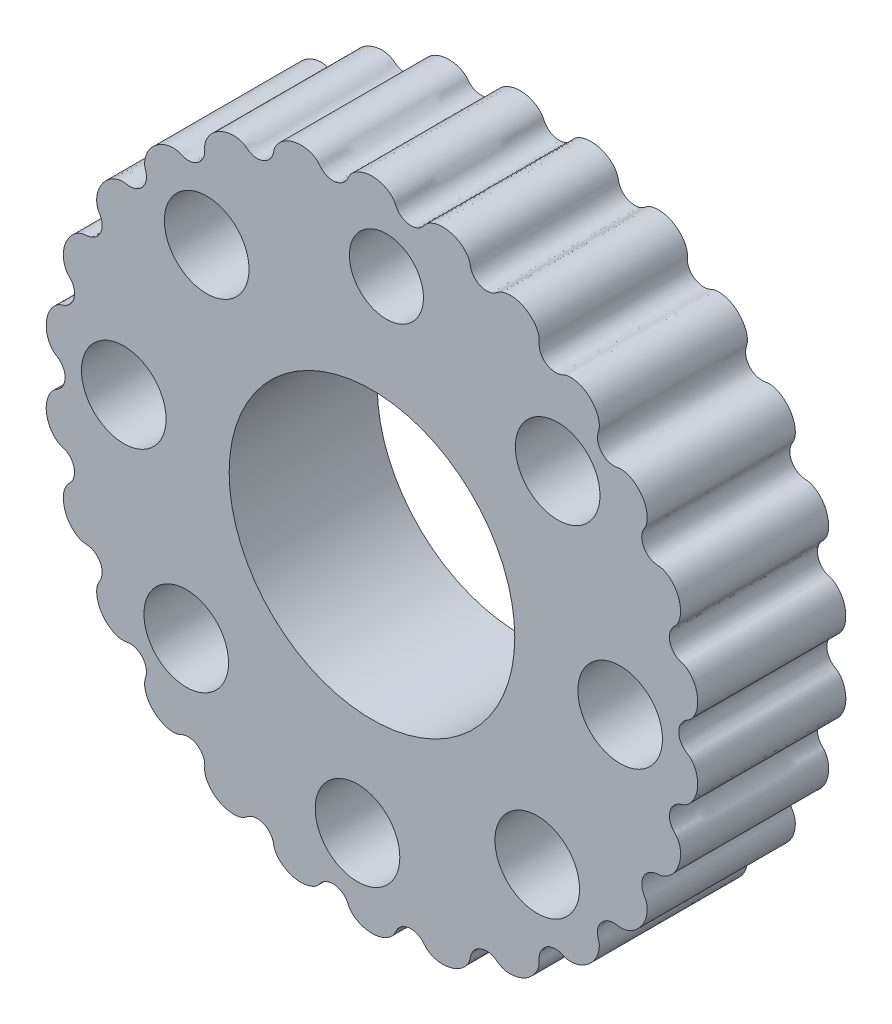
SolidWorks part; units mm, degrees
ref_plane "Front Plane" through (0, 0, 0) normal (0, 0, 1) x (1, 0, 0)
ref_plane "Top Plane" through (0, 0, 0) normal (0, 1, 0) x (1, 0, 0)
ref_plane "Right Plane" through (0, 0, 0) normal (1, 0, 0) x (0, 0, -1)
ref_plane "Plane1"
sketch "Sketch1" plane through (0, 0, 0) normal (0, 0, 1) x (1, 0, 0)
  circle A0 centre (23.4602, -1.3664) radius 4
  circle A1 centre (17.5551, 15.6227) radius 4
  circle A2 centre (1.3664, 23.4602) radius 4
  circle A3 centre (-15.6227, 17.5551) radius 4
  circle A4 centre (-23.4602, 1.3664) radius 4
  circle A5 centre (-17.5551, -15.6227) radius 4
  circle A6 centre (-1.3664, -23.4602) radius 4
  circle A7 centre (15.6227, -17.5551) radius 4
  circle A8 centre (0, 0) radius 13.5
  spline S0 degree 3 poles (29, 0) (29, -0.3768) (29.1535, -0.7032) (29.2804, -0.8839) (29.4951, -1.1897) (29.6235, -1.2426) (29.7, -1.2958) (29.8542, -1.4032) (29.8827, -1.413) (29.9346, -1.4485) (30.0574, -1.5322) (30.2266, -1.6673) (30.4081, -1.9555) (30.6633, -2.3609) (30.8614, -3.0668) (30.7707, -3.763) (30.6897, -4.3835) (30.3903, -4.9545) (30.0794, -5.2897) (29.8505, -5.5365) (29.6366, -5.6604) (29.4954, -5.7232) (29.4221, -5.7558) (29.3787, -5.7696) (29.2726, -5.805) (29.2187, -5.823) (29.1538, -5.8344) (28.9703, -5.9277) (28.8487, -5.9895) (28.6383, -6.0836) (28.4024, -6.4106) (28.2302, -6.6494) (28.1014, -7.0439) (28.114, -7.3663) (28.13, -7.7749) (28.2721, -8.0058) (28.3561, -8.139) (28.5057, -8.3761) (28.5682, -8.4123) (28.6126, -8.4587) (28.7112, -8.5615) (28.7444, -8.5938) (28.8088, -8.6819) (28.9486, -8.8731) (29.1514, -9.2784) (29.1753, -9.8433) (29.2016, -10.4629) (28.9684, -11.2228) (28.5673, -11.7445) (28.2242, -12.1907) (27.7962, -12.4491) (27.512, -12.5503) (27.3588, -12.6048) (27.2544, -12.621) (27.1583, -12.631) (27.0994, -12.6372) (27.0677, -12.6315) (26.8731, -12.6585) (26.7882, -12.6702) (26.6656, -12.6757) (26.4169, -12.7864) (26.2329, -12.8684) (25.9467, -13.0438) (25.7404, -13.3693) (25.5449, -13.678) (25.4898, -14.0569) (25.5065, -14.2975) (25.5338, -14.6901) (25.6313, -14.8203) (25.6773, -14.913) (25.7672, -15.0947) (25.7908, -15.1176) (25.819, -15.1687) (25.8858, -15.2896) (25.9587, -15.4408) (26.0003, -15.7215) (26.0635, -16.1484) (25.9783, -16.8383) (25.624, -17.4359) (25.2735, -18.0271) (24.6847, -18.475) (24.2049, -18.6519) (23.8505, -18.7825) (23.5839, -18.7865) (23.4237, -18.7723) (23.3532, -18.766) (23.3135, -18.758) (23.193, -18.7391) (23.1305, -18.7293) (23.0571, -18.7044) (22.817, -18.7127) (22.666, -18.718) (22.4117, -18.7282) (22.0741, -18.9277) (21.8037, -19.0874) (21.537, -19.4066) (21.4267, -19.6888) (21.2703, -20.0892) (21.3164, -20.3323) (21.3352, -20.4729) (21.3697, -20.7318) (21.4008, -20.775) (21.4173, -20.8314) (21.4554, -20.962) (21.476, -21.0337) (21.4871, -21.194) (21.5077, -21.4931) (21.432, -22.0351) (21.1005, -22.5638) (20.7525, -23.1188) (20.1283, -23.5982) (19.5445, -23.7905) (19.0833, -23.9425) (18.6768, -23.9306) (18.4374, -23.8827) (18.3183, -23.8589) (18.2417, -23.8315) (18.1648, -23.8002) (18.1153, -23.78) (18.0821, -23.7599) (17.9302, -23.7036) (17.8502, -23.674) (17.7421, -23.6178) (17.4519, -23.5986) (17.2532, -23.5854) (16.9238, -23.6055) (16.5911, -23.7932) (16.2828, -23.9672) (16.0549, -24.2657) (15.9532, -24.4853) (15.7864, -24.8455) (15.8095, -25.0146) (15.8061, -25.1217) (15.7995, -25.3288) (15.8106, -25.3619) (15.8121, -25.419) (15.8156, -25.554) (15.8124, -25.7044) (15.7327, -25.9537) (15.6076, -26.3448) (15.2434, -26.9124) (14.671, -27.2924) (14.1247, -27.6552) (13.4277, -27.8145) (12.9077, -27.7783) (12.4959, -27.7496) (12.2125, -27.6253) (12.0576, -27.5329) (11.9881, -27.4915) (11.9482, -27.4616) (11.8709, -27.4033) (11.8233, -27.3673) (11.7888, -27.3192) (11.5576, -27.1982) (11.4393, -27.1363) (11.2501, -27.0314) (10.8867, -27.0172) (10.599, -27.006) (10.2014, -27.1117) (9.9356, -27.3019) (9.6266, -27.5231) (9.5017, -27.7618) (9.4329, -27.9087) (9.301, -28.1902) (9.3096, -28.2703) (9.2956, -28.3375) (9.2644, -28.4872) (9.2586, -28.5276) (9.225, -28.6271) (9.1526, -28.842) (8.9513, -29.2246) (8.5213, -29.5648) (8.0513, -29.9367) (7.3217, -30.1953) (6.6665, -30.1855) (6.1495, -30.1778) (5.702, -30.0198) (5.428, -29.8555) (5.2317, -29.7378) (5.1254, -29.6318) (5.0489, -29.545) (5.0104, -29.5012) (4.9895, -29.4704) (4.8985, -29.3641) (4.8484, -29.3055) (4.797, -29.2149) (4.5489, -29.0464) (4.3992, -28.9447) (4.1364, -28.7982) (3.7557, -28.7793) (3.4144, -28.7624) (3.0427, -28.892) (2.8246, -29.0387) (2.4844, -29.2675) (2.4056, -29.4474) (2.3446, -29.5491) (2.2297, -29.7406) (2.2241, -29.781) (2.1999, -29.8314) (2.143, -29.9499) (2.0908, -30.0507) (1.9482, -30.2096) (1.7042, -30.4816) (1.1811, -30.8377) (0.5184, -30.9547) (-0.1433, -31.0716) (-0.8912, -30.9256) (-1.3839, -30.6514) (-1.7244, -30.4618) (-1.9423, -30.2342) (-2.0587, -30.0727) (-2.1328, -29.9699) (-2.1641, -29.907) (-2.2104, -29.8094) (-2.2297, -29.7686) (-2.2472, -29.7236) (-2.3086, -29.6118) (-2.354, -29.5292) (-2.4036, -29.3984) (-2.6485, -29.1765) (-2.8114, -29.029) (-3.1148, -28.8364) (-3.4891, -28.7894) (-3.8512, -28.7438) (-4.1885, -28.8477) (-4.3847, -28.9488) (-4.7171, -29.1199) (-4.7917, -29.2448) (-4.8562, -29.3161) (-4.9839, -29.457) (-4.9977, -29.4858) (-5.0369, -29.5312) (-5.1335, -29.6432) (-5.276, -29.7878) (-5.5725, -29.9342) (-5.9813, -30.1361) (-6.6691, -30.2631) (-7.3372, -30.1181) (-8.0054, -29.9731) (-8.5993, -29.5653) (-8.9067, -29.1864) (-9.1084, -28.9378) (-9.1972, -28.7228) (-9.2396, -28.5812) (-9.2583, -28.5188) (-9.2682, -28.4729) (-9.2832, -28.3986) (-9.2922, -28.3537) (-9.2988, -28.3029) (-9.3344, -28.1756) (-9.3615, -28.0789) (-9.3833, -27.9276) (-9.5864, -27.6486) (-9.7241, -27.4594) (-10.0027, -27.2036) (-10.3581, -27.0894) (-10.7123, -26.9756) (-11.0474, -27.018) (-11.2473, -27.0744) (-11.6072, -27.1758) (-11.6905, -27.2733) (-11.7631, -27.3241) (-11.9144, -27.4301) (-11.9326, -27.4513) (-11.9905, -27.4903) (-12.1265, -27.582) (-12.364, -27.7112) (-12.7623, -27.7637) (-13.2625, -27.8296) (-13.98, -27.7125) (-14.5617, -27.3617) (-15.1424, -27.0114) (-15.5442, -26.46) (-15.6987, -26.0512) (-15.796, -25.7936) (-15.8116, -25.6098) (-15.8127, -25.4806) (-15.8131, -25.431) (-15.8112, -25.3906) (-15.8081, -25.3148) (-15.806, -25.2642) (-15.7987, -25.2039) (-15.8099, -25.0483) (-15.8182, -24.933) (-15.8173, -24.7503) (-15.978, -24.4341) (-16.0929, -24.2081) (-16.344, -23.9163) (-16.6528, -23.7603) (-17.0099, -23.5797) (-17.3332, -23.5839) (-17.5212, -23.6047) (-17.8534, -23.6414) (-17.9327, -23.7033) (-18.0037, -23.7323) (-18.1561, -23.7944) (-18.1838, -23.8103) (-18.262, -23.8364) (-18.4404, -23.8958) (-18.7757, -23.9629) (-19.2368, -23.8716) (-19.7732, -23.7654) (-20.4268, -23.4061) (-20.8581, -22.8954) (-21.2862, -22.3886) (-21.4709, -21.7796) (-21.4889, -21.3946) (-21.5006, -21.1457) (-21.4689, -21.0138) (-21.4316, -20.881) (-21.4196, -20.8384) (-21.4053, -20.798) (-21.3781, -20.6911) (-21.3584, -20.6139) (-21.3146, -20.5126) (-21.3209, -20.2211) (-21.3252, -20.0275) (-21.3677, -19.6993) (-21.5965, -19.3708) (-21.805, -19.0713) (-22.1447, -18.8656) (-22.3836, -18.7883) (-22.7753, -18.6615) (-22.9389, -18.7099) (-23.0449, -18.72) (-23.2441, -18.739) (-23.2757, -18.7532) (-23.3323, -18.7614) (-23.4706, -18.7816) (-23.6339, -18.7969) (-23.9104, -18.7378) (-24.318, -18.6506) (-24.9112, -18.3483) (-25.344, -17.8314) (-25.7763, -17.3151) (-26.009, -16.6207) (-26.0223, -16.0997) (-26.0305, -15.7796) (-25.9715, -15.5311) (-25.9128, -15.3722) (-25.8794, -15.2821) (-25.8488, -15.2219) (-25.8135, -15.1588) (-25.7908, -15.1181) (-25.7677, -15.0833) (-25.7129, -14.9818) (-25.6787, -14.9186) (-25.6238, -14.8384) (-25.5603, -14.6098) (-25.5153, -14.4476) (-25.4561, -14.1735) (-25.552, -13.8037) (-25.6387, -13.4698) (-25.8918, -13.1306) (-26.1184, -12.9613) (-26.4466, -12.7161) (-26.6525, -12.6984) (-26.7739, -12.6749) (-26.9988, -12.6314) (-27.0428, -12.6411) (-27.0985, -12.6365) (-27.2342, -12.6254) (-27.3357, -12.6149) (-27.5268, -12.5449) (-27.8511, -12.4261) (-28.3537, -12.0954) (-28.7066, -11.5466) (-29.0604, -10.9965) (-29.2219, -10.2615) (-29.1644, -9.6901) (-29.1166, -9.2153) (-28.9463, -8.8757) (-28.8213, -8.6992) (-28.7612, -8.6144) (-28.7198, -8.5699) (-28.6508, -8.4983) (-28.6171, -8.4633) (-28.5778, -8.4304) (-28.4799, -8.3105) (-28.416, -8.2322) (-28.3073, -8.1242) (-28.1992, -7.8144) (-28.123, -7.5961) (-28.071, -7.229) (-28.1747, -6.8756) (-28.2827, -6.5076) (-28.5171, -6.2492) (-28.6801, -6.1162) (-28.9604, -5.8874) (-29.0858, -5.8722) (-29.1681, -5.8416) (-29.337, -5.7787) (-29.3662, -5.775) (-29.4289, -5.7508) (-29.5759, -5.6941) (-29.8003, -5.5836) (-30.0604, -5.31) (-30.3935, -4.9595) (-30.7169, -4.3332) (-30.7818, -3.6653) (-30.8458, -3.0063) (-30.656, -2.3551) (-30.4157, -1.9677) (-30.2771, -1.7444) (-30.1351, -1.6043) (-30.0301, -1.5193) (-29.9574, -1.4605) (-29.9166, -1.4356) (-29.8137, -1.3706) (-29.7667, -1.341) (-29.708, -1.3143) (-29.5579, -1.1868) (-29.4553, -1.0998) (-29.2724, -0.9632) (-29.1161, -0.5848) (-29.0009, -0.3057) (-28.9698, 0.1259) (-29.0654, 0.4425) (-29.1841, 0.8355) (-29.3773, 1.0194) (-29.4897, 1.1258) (-29.6904, 1.3157) (-29.7572, 1.3349) (-29.8106, 1.3687) (-29.9298, 1.444) (-29.9717, 1.4689) (-30.0584, 1.5428) (-30.2439, 1.701) (-30.5415, 2.06) (-30.6943, 2.6142) (-30.8613, 3.2202) (-30.8013, 4.0179) (-30.5269, 4.6132) (-30.2894, 5.1284) (-29.9282, 5.4693) (-29.6815, 5.6237) (-29.5751, 5.6903) (-29.4924, 5.7268) (-29.4191, 5.7546) (-29.3615, 5.7764) (-29.3277, 5.7831) (-29.1802, 5.8371) (-29.1098, 5.8629) (-29.0101, 5.8851) (-28.7932, 6.032) (-28.6486, 6.13) (-28.4211, 6.3101) (-28.2591, 6.6536) (-28.115, 6.959) (-28.0901, 7.3587) (-28.146, 7.6238) (-28.233, 8.0358) (-28.3787, 8.1814) (-28.4539, 8.278) (-28.5962, 8.4604) (-28.6326, 8.479) (-28.6715, 8.5199) (-28.763, 8.6159) (-28.8382, 8.6995) (-28.9365, 8.8892) (-29.1068, 9.218) (-29.2558, 9.8476) (-29.1217, 10.5193) (-28.9876, 11.1907) (-28.5674, 11.8414) (-28.1295, 12.1955) (-27.7806, 12.4777) (-27.461, 12.5803) (-27.2753, 12.6144) (-27.1996, 12.6284) (-27.1508, 12.6324) (-27.058, 12.6397) (-27.0015, 12.6441) (-26.9433, 12.6361) (-26.7233, 12.6854) (-26.6027, 12.7125) (-26.4096, 12.7473) (-26.1284, 12.9539) (-25.9109, 13.1136) (-25.6628, 13.4275) (-25.5663, 13.7523) (-25.453, 14.134) (-25.5114, 14.4283) (-25.5572, 14.5982) (-25.6376, 14.8968) (-25.7013, 14.962) (-25.7367, 15.0249) (-25.8126, 15.1598) (-25.8327, 15.1886) (-25.8686, 15.2659) (-25.9518, 15.4452) (-26.061, 15.7967) (-26.01, 16.2903) (-25.9515, 16.8559) (-25.6388, 17.5553) (-25.1623, 18.0295) (-24.7487, 18.441) (-24.2464, 18.6693) (-23.892, 18.7416) (-23.6537, 18.7902) (-23.494, 18.7817) (-23.375, 18.7672) (-23.3156, 18.7599) (-23.2803, 18.7506) (-23.1376, 18.7309) (-23.061, 18.7203) (-22.9621, 18.6866) (-22.6645, 18.7252) (-22.4847, 18.7486) (-22.1905, 18.8139) (-21.8935, 19.0526) (-21.627, 19.2669) (-21.4355, 19.6104) (-21.37, 19.8646) (-21.2676, 20.2613) (-21.328, 20.4476) (-21.3498, 20.564) (-21.3908, 20.7831) (-21.4134, 20.817) (-21.4287, 20.8708) (-21.4646, 20.9971) (-21.4925, 21.1077) (-21.4909, 21.322) (-21.4883, 21.6876) (-21.3324, 22.3006) (-20.9141, 22.8271) (-20.4969, 23.3522) (-19.8418, 23.7383) (-19.2919, 23.8601) (-18.9242, 23.9415) (-18.6172, 23.9206) (-18.4224, 23.8796) (-18.3156, 23.8572) (-18.2436, 23.8318) (-18.1736, 23.8037) (-18.1304, 23.7864) (-18.0938, 23.7688) (-17.9991, 23.7304) (-17.9282, 23.7016) (-17.8468, 23.6417) (-17.5259, 23.6052) (-17.3453, 23.5847) (-17.0425, 23.5774) (-16.6954, 23.7395) (-16.3857, 23.8842) (-16.1186, 24.1719) (-15.9945, 24.4026) (-15.8013, 24.7619) (-15.8149, 24.9569) (-15.8082, 25.075) (-15.7955, 25.2966) (-15.8092, 25.3354) (-15.8112, 25.3912) (-15.8159, 25.5219) (-15.8166, 25.6338) (-15.7656, 25.8382) (-15.6784, 26.1874) (-15.3894, 26.7385) (-14.8669, 27.1506) (-14.3457, 27.5617) (-13.6251, 27.7892) (-13.0592, 27.7842) (-12.6994, 27.7811) (-12.4096, 27.6997) (-12.223, 27.6178) (-12.089, 27.5589) (-12.0124, 27.5078) (-11.9354, 27.4515) (-11.8996, 27.4253) (-11.8677, 27.3989) (-11.7841, 27.339) (-11.7249, 27.2966) (-11.6545, 27.2288) (-11.4118, 27.1307) (-11.2514, 27.0658) (-10.9753, 26.9745) (-10.591, 27.0342) (-10.2451, 27.088) (-9.8867, 27.3072) (-9.6991, 27.511) (-9.423, 27.811) (-9.3864, 28.0067) (-9.3505, 28.1214) (-9.2836, 28.3352) (-9.2876, 28.3777) (-9.2763, 28.4322) (-9.2486, 28.5659) (-9.2229, 28.6754) (-9.1199, 28.868) (-8.9499, 29.1858) (-8.5383, 29.6467) (-7.9371, 29.9196) (-7.3363, 30.1923) (-6.5877, 30.2423) (-6.0406, 30.1047) (-5.6141, 29.9974) (-5.3226, 29.8039) (-5.1687, 29.6659) (-5.092, 29.5972) (-5.0504, 29.5488) (-4.993, 29.4787) (-4.9629, 29.4418) (-4.9364, 29.402) (-4.8378, 29.296) (-4.7759, 29.2295) (-4.6957, 29.124) (-4.4418, 28.9797) (-4.2603, 28.8765) (-3.9418, 28.7541) (-3.5679, 28.7815) (-3.1975, 28.8087) (-2.8689, 28.9896) (-2.691, 29.1394) (-2.3931, 29.3903) (-2.3498, 29.5357) (-2.3028, 29.6225) (-2.2089, 29.7958) (-2.2036, 29.8258) (-2.1759, 29.8802) (-2.1105, 30.0087) (-2.0098, 30.1776) (-1.7682, 30.3852) (-1.4156, 30.6881) (-0.7524, 30.9888) (-0.0462, 30.9996) (0.5923, 31.0095) (1.2195, 30.7852) (1.605, 30.5124) (1.8911, 30.3099) (2.0459, 30.1047) (2.1271, 29.9687) (2.1674, 29.9012) (2.1866, 29.8595) (2.233, 29.7615) (2.2574, 29.7101) (2.2757, 29.6475) (2.3926, 29.4734) (2.467, 29.3626) (2.5819, 29.1735) (2.9175, 28.9809) (3.168, 28.8371) (3.5705, 28.7467) (3.8942, 28.7925) (4.2967, 28.8494) (4.5186, 29.0167) (4.6452, 29.1172) (4.8699, 29.2955) (4.9004, 29.3654) (4.9422, 29.4163) (5.0342, 29.5284) (5.0599, 29.5628) (5.1339, 29.6337) (5.2974, 29.7904) (5.6534, 30.0364) (6.1935, 30.1383) (6.7871, 30.2502) (7.5608, 30.1369) (8.1381, 29.8188) (8.5814, 29.5746) (8.8978, 29.235) (9.0635, 28.9661) (9.1817, 28.7742) (9.2288, 28.6299) (9.2566, 28.5195) (9.2721, 28.4578) (9.2751, 28.4235) (9.3097, 28.2732) (9.3271, 28.1974) (9.3312, 28.0918) (9.4736, 27.8277) (9.5602, 27.6672) (9.7277, 27.415) (10.0569, 27.2235) (10.3531, 27.0512) (10.7416, 26.9964) (11.0012, 27.0259) (11.4075, 27.0722) (11.5587, 27.1944) (11.6592, 27.2559) (11.8484, 27.3716) (11.872, 27.4044) (11.9168, 27.4378) (12.0223, 27.5162) (12.1171, 27.5822) (12.32, 27.6568) (12.6643, 27.7836) (13.2928, 27.8533) (13.9323, 27.6481) (14.5689, 27.4437) (15.1594, 26.9699) (15.4677, 26.5005) (15.6598, 26.2079) (15.7515, 25.9314) (15.7876, 25.7371) (15.8135, 25.5976) (15.8146, 25.5084) (15.812, 25.4139) (15.8107, 25.37) (15.8071, 25.3286) (15.8054, 25.2261) (15.8042, 25.152) (15.7873, 25.0536) (15.8486, 24.7902) (15.8886, 24.6178) (15.9775, 24.3322) (16.2522, 24.0528) (16.5, 23.8009) (16.884, 23.6413) (17.1534, 23.6073) (17.5554, 23.5566) (17.7305, 23.6379) (17.8424, 23.6734) (18.0522, 23.7399) (18.0838, 23.7663) (18.1351, 23.7879) (18.2607, 23.8407) (18.372, 23.8837) (18.5979, 23.9067) (18.964, 23.9439) (19.5818, 23.8572) (20.1449, 23.51) (20.7265, 23.1512) (21.1918, 22.5303) (21.3724, 21.9933) (21.5123, 21.5773) (21.5021, 21.2423) (21.4707, 21.0529) (21.4559, 20.9637) (21.4417, 20.9149) (21.4113, 20.811) (21.396, 20.7587) (21.3706, 20.7041) (21.3403, 20.5085) (21.3217, 20.3886) (21.2811, 20.1993) (21.3727, 19.8542) (21.4432, 19.5887) (21.6547, 19.2307) (21.9337, 19.0214) (22.2541, 18.781) (22.5487, 18.735) (22.7224, 18.7188) (23.0278, 18.6903) (23.1091, 18.7262) (23.1795, 18.737) (23.3314, 18.7603) (23.3663, 18.7688) (23.4538, 18.7747) (23.6557, 18.7882) (24.0345, 18.7615) (24.4844, 18.5281) (24.9872, 18.2673) (25.5164, 17.7299) (25.7846, 17.1247) (26.0344, 16.5607) (26.0544, 15.9812) (25.984, 15.6272) (25.9382, 15.3975) (25.8769, 15.273) (25.8165, 15.1641) (25.7953, 15.126) (25.7738, 15.0918) (25.7285, 15.0103) (25.6952, 14.9504) (25.6409, 14.8794) (25.5698, 14.6426) (25.5237, 14.489) (25.4572, 14.2313) (25.5384, 13.8606) (25.6109, 13.53) (25.8522, 13.1716) (26.0831, 12.9885) (26.4073, 12.7314) (26.6245, 12.7057) (26.7511, 12.6794) (26.9837, 12.6313) (27.031, 12.6419) (27.0873, 12.6374) (27.2178, 12.627) (27.3027, 12.6189) (27.4671, 12.5656) (27.7686, 12.4677) (28.2609, 12.1788) (28.6308, 11.6587) (29.0015, 11.1375) (29.2039, 10.413) (29.1744, 9.8229) (29.1508, 9.3501) (29.0003, 8.9827) (28.873, 8.7772) (28.8085, 8.6732) (28.755, 8.6098) (28.6995, 8.5497) (28.6691, 8.5168) (28.6401, 8.4887) (28.5753, 8.4192) (28.5276, 8.3681) (28.4554, 8.3132) (28.3234, 8.0848) (28.2409, 7.9422) (28.1147, 7.6975) (28.1129, 7.3134) (28.1113, 6.9705) (28.2698, 6.5726) (28.4502, 6.3478) (28.708, 6.0265) (28.9074, 5.9561) (29.0214, 5.9028) (29.2318, 5.8044) (29.278, 5.8033) (29.3312, 5.7855) (29.4604, 5.7424) (29.552, 5.7099) (29.7161, 5.6015) (29.9966, 5.4162) (30.4023, 4.9904) (30.6205, 4.3846) (30.8435, 3.7652) (30.8343, 3.0004) (30.6428, 2.4484) (30.4865, 1.9983) (30.2416, 1.7041) (30.0764, 1.5584) (29.9937, 1.4856) (29.9406, 1.4506) (29.855, 1.3967) (29.8122, 1.3697) (29.766, 1.3487) (29.6294, 1.2444) (29.5505, 1.1842) (29.4269, 1.1035) (29.2607, 0.8551) (29.139, 0.6733) (29, 0.3574) (29, 0) (29, -0.3768) (29.1535, -0.7032) knots -0.259182 0 0 0 0.273271 0.273271 0.273271 0.73572 0.73572 0.73572 1.667811 1.667811 1.667811 3.867641 3.867641 3.867641 6.962071 6.962071 6.962071 9.72018 9.72018 9.72018 11.750932 11.750932 11.750932 12.805416 12.805416 12.805416 13.340183 13.340183 13.340183 13.694712 13.694712 13.694712 13.953634 13.953634 13.953634 14.281743 14.281743 14.281743 14.865962 14.865962 14.865962 16.163063 16.163063 16.163063 18.977016 18.977016 18.977016 22.06375 22.06375 22.06375 24.703877 24.703877 24.703877 26.127104 26.127104 26.127104 26.999377 26.999377 26.999377 27.380316 27.380316 27.380316 27.662164 27.662164 27.662164 27.929335 27.929335 27.929335 28.36543 28.36543 28.36543 29.219102 29.219102 29.219102 31.238876 31.238876 31.238876 34.311171 34.311171 34.311171 37.350654 37.350654 37.350654 39.595071 39.595071 39.595071 40.582862 40.582862 40.582862 41.095396 41.095396 41.095396 41.417912 41.417912 41.417912 41.676264 41.676264 41.676264 42.042748 42.042748 42.042748 42.717753 42.717753 42.717753 44.281405 44.281405 44.281405 47.199396 47.199396 47.199396 50.26224 50.26224 50.26224 52.682066 52.682066 52.682066 53.886048 53.886048 53.886048 54.662443 54.662443 54.662443 55.071214 55.071214 55.071214 55.351053 55.351053 55.351053 55.610487 55.610487 55.610487 56.036033 56.036033 56.036033 56.858516 56.858516 56.858516 58.803695 58.803695 58.803695 61.854553 61.854553 61.854553 64.766502 64.766502 64.766502 67.073013 67.073013 67.073013 68.107662 68.107662 68.107662 68.744786 68.744786 68.744786 69.071017 69.071017 69.071017 69.329235 69.329235 69.329235 69.62948 69.62948 69.62948 70.205013 70.205013 70.205013 71.488475 71.488475 71.488475 74.258794 74.258794 74.258794 77.286841 77.286841 77.286841 79.676527 79.676527 79.676527 81.388111 81.388111 81.388111 82.251079 82.251079 82.251079 82.726345 82.726345 82.726345 83.013148 83.013148 83.013148 83.270219 83.270219 83.270219 83.671043 83.671043 83.671043 84.425434 84.425434 84.425434 86.197564 86.197564 86.197564 89.229028 89.229028 89.229028 92.255429 92.255429 92.255429 94.347183 94.347183 94.347183 95.679653 95.679653 95.679653 96.236499 96.236499 96.236499 96.647911 96.647911 96.647911 96.921509 96.921509 96.921509 97.186211 97.186211 97.186211 97.634596 97.634596 97.634596 98.521506 98.521506 98.521506 100.708447 100.708447 100.708447 103.723018 103.723018 103.723018 106.738574 106.738574 106.738574 108.717179 108.717179 108.717179 109.589099 109.589099 109.589099 110.116095 110.116095 110.116095 110.516709 110.516709 110.516709 110.78834 110.78834 110.78834 111.059087 111.059087 111.059087 111.546664 111.546664 111.546664 112.56309 112.56309 112.56309 114.952876 114.952876 114.952876 117.954345 117.954345 117.954345 120.950868 120.950868 120.950868 122.839183 122.839183 122.839183 123.565209 123.565209 123.565209 124.049982 124.049982 124.049982 124.409254 124.409254 124.409254 124.666117 124.666117 124.666117 124.963231 124.963231 124.963231 125.488153 125.488153 125.488153 126.614587 126.614587 126.614587 129.185256 129.185256 129.185256 132.175578 132.175578 132.175578 135.143154 135.143154 135.143154 137.062298 137.062298 137.062298 137.678032 137.678032 137.678032 138.12276 138.12276 138.12276 138.41814 138.41814 138.41814 138.687346 138.687346 138.687346 139.128622 139.128622 139.128622 139.957815 139.957815 139.957815 141.985456 141.985456 141.985456 144.974918 144.974918 144.974918 147.960744 147.960744 147.960744 149.795195 149.795195 149.795195 150.835631 150.835631 150.835631 151.506978 151.506978 151.506978 151.924607 151.924607 151.924607 152.220913 152.220913 152.220913 152.488444 152.488444 152.488444 152.875803 152.875803 152.875803 153.593202 153.593202 153.593202 155.341578 155.341578 155.341578 158.308623 158.308623 158.308623 161.282783 161.282783 161.282783 163.754107 163.754107 163.754107 164.941245 164.941245 164.941245 165.522436 165.522436 165.522436 165.902275 165.902275 165.902275 166.170022 166.170022 166.170022 166.448877 166.448877 166.448877 166.928483 166.928483 166.928483 167.91343 167.91343 167.91343 170.22349 170.22349 170.22349 173.182408 173.182408 173.182408 176.101433 176.101433 176.101433 177.784641 177.784641 177.784641 178.949961 178.949961 178.949961 179.481526 179.481526 179.481526 179.844765 179.844765 179.844765 180.11262 180.11262 180.11262 180.44515 180.44515 180.44515 181.038587 181.038587 181.038587 182.362931 182.362931 182.362931 185.19794 185.19794 185.19794 188.297733 188.297733 188.297733 190.98058 190.98058 190.98058 192.137767 192.137767 192.137767 193.047282 193.047282 193.047282 193.481577 193.481577 193.481577 193.771277 193.771277 193.771277 194.028767 194.028767 194.028767 194.428899 194.428899 194.428899 195.185223 195.185223 195.185223 196.961489 196.961489 196.961489 200.040027 200.040027 200.040027 203.116656 203.116656 203.116656 205.567958 205.567958 205.567958 206.566423 206.566423 206.566423 207.174229 207.174229 207.174229 207.507609 207.507609 207.507609 207.765441 207.765441 207.765441 208.068419 208.068419 208.068419 208.600568 208.600568 208.600568 209.742311 209.742311 209.742311 212.39082 212.39082 212.39082 215.425744 215.425744 215.425744 218.059815 218.059815 218.059815 219.830399 219.830399 219.830399 220.714703 220.714703 220.714703 221.188761 221.188761 221.188761 221.475293 221.475293 221.475293 221.732377 221.732377 221.732377 222.133637 222.133637 222.133637 222.888965 222.888965 222.888965 224.663464 224.663464 224.663464 227.692233 227.692233 227.692233 230.71307 230.71307 230.71307 232.733178 232.733178 232.733178 233.840283 233.840283 233.840283 234.522989 234.522989 234.522989 235.034262 235.034262 235.034262 235.322087 235.322087 235.322087 235.578925 235.578925 235.578925 235.978901 235.978901 235.978901 236.729105 236.729105 236.729105 238.488881 238.488881 238.488881 241.493736 241.493736 241.493736 244.491666 244.491666 244.491666 246.39846 246.39846 246.39846 247.767079 247.767079 247.767079 248.403234 248.403234 248.403234 248.854331 248.854331 248.854331 249.152317 249.152317 249.152317 249.420576 249.420576 249.420576 249.815578 249.815578 249.815578 250.552381 250.552381 250.552381 252.35891 252.35891 252.35891 255.34034 255.34034 255.34034 258.319628 258.319628 258.319628 260.642143 260.642143 260.642143 261.798582 261.798582 261.798582 262.405476 262.405476 262.405476 262.786705 262.786705 262.786705 263.059324 263.059324 263.059324 263.329504 263.329504 263.329504 263.781667 263.781667 263.781667 264.684781 264.684781 264.684781 266.81857 266.81857 266.81857 269.932168 269.932168 269.932168 272.746787 272.746787 272.746787 274.835557 274.835557 274.835557 275.872957 275.872957 275.872957 276.417338 276.417338 276.417338 276.763895 276.763895 276.763895 277.022592 277.022592 277.022592 277.344291 277.344291 277.344291 277.915174 277.915174 277.915174 279.172481 279.172481 279.172481 281.949908 281.949908 281.949908 285.002315 285.002315 285.002315 287.345993 287.345993 287.345993 289.017912 289.017912 289.017912 289.951463 289.951463 289.951463 290.421965 290.421965 290.421965 290.707776 290.707776 290.707776 290.964901 290.964901 290.964901 291.367403 291.367403 291.367403 292.125519 292.125519 292.125519 293.907174 293.907174 293.907174 296.93058 296.93058 296.93058 299.940937 299.940937 299.940937 301.817782 301.817782 301.817782 303.165524 303.165524 303.165524 303.792603 303.792603 303.792603 304.246764 304.246764 304.246764 304.544214 304.544214 304.544214 304.812425 304.812425 304.812425 305.212705 305.212705 305.212705 305.962975 305.962975 305.962975 307.800356 307.800356 307.800356 310.778197 310.778197 310.778197 313.85456 313.85456 313.85456 316.2375 316.2375 316.2375 317.359832 317.359832 317.359832 317.924658 317.924658 317.924658 318.271121 318.271121 318.271121 318.537585 318.537585 318.537585 318.84351 318.84351 318.84351 319.381571 319.381571 319.381571 320.541854 320.541854 320.541854 323.218568 323.218568 323.218568 326.209995 326.209995 326.209995 328.997402 328.997402 328.997402 330.80632 330.80632 330.80632 331.438702 331.438702 331.438702 331.903936 331.903936 331.903936 332.205598 332.205598 332.205598 332.474634 332.474634 332.474634 332.852361 332.852361 332.852361 333.546306 333.546306 333.546306 335.153316 335.153316 335.153316 338.101884 338.101884 338.101884 341.056869 341.056869 341.056869 343.424761 343.424761 343.424761 344.622494 344.622494 344.622494 345.277713 345.277713 345.277713 345.759386 345.759386 345.759386 346.060354 346.060354 346.060354 346.329099 346.329099 346.329099 346.713058 346.713058 346.713058 347.421679 347.421679 347.421679 349.14232 349.14232 349.14232 352.084779 352.084779 352.084779 355.093551 355.093551 355.093551 357.546775 357.546775 357.546775 358.773388 358.773388 358.773388 359.386694 359.386694 359.386694 359.740818 359.740818 359.740818 360 360 360 360.273271 360.273271 360.273271 weights 1 1 1 1 1 1 1 1 1 1 1 1 1 1 1 1 1 1 1 1 1 1 1 1 1 1 1 1 1 1 1 1 1 1 1 1 1 1 1 1 1 1 1 1 1 1 1 1 1 1 1 1 1 1 1 1 1 1 1 1 1 1 1 1 1 1 1 1 1 1 1 1 1 1 1 1 1 1 1 1 1 1 1 1 1 1 1 1 1 1 1 1 1 1 1 1 1 1 1 1 1 1 1 1 1 1 1 1 1 1 1 1 1 1 1 1 1 1 1 1 1 1 1 1 1 1 1 1 1 1 1 1 1 1 1 1 1 1 1 1 1 1 1 1 1 1 1 1 1 1 1 1 1 1 1 1 1 1 1 1 1 1 1 1 1 1 1 1 1 1 1 1 1 1 1 1 1 1 1 1 1 1 1 1 1 1 1 1 1 1 1 1 1 1 1 1 1 1 1 1 1 1 1 1 1 1 1 1 1 1 1 1 1 1 1 1 1 1 1 1 1 1 1 1 1 1 1 1 1 1 1 1 1 1 1 1 1 1 1 1 1 1 1 1 1 1 1 1 1 1 1 1 1 1 1 1 1 1 1 1 1 1 1 1 1 1 1 1 1 1 1 1 1 1 1 1 1 1 1 1 1 1 1 1 1 1 1 1 1 1 1 1 1 1 1 1 1 1 1 1 1 1 1 1 1 1 1 1 1 1 1 1 1 1 1 1 1 1 1 1 1 1 1 1 1 1 1 1 1 1 1 1 1 1 1 1 1 1 1 1 1 1 1 1 1 1 1 1 1 1 1 1 1 1 1 1 1 1 1 1 1 1 1 1 1 1 1 1 1 1 1 1 1 1 1 1 1 1 1 1 1 1 1 1 1 1 1 1 1 1 1 1 1 1 1 1 1 1 1 1 1 1 1 1 1 1 1 1 1 1 1 1 1 1 1 1 1 1 1 1 1 1 1 1 1 1 1 1 1 1 1 1 1 1 1 1 1 1 1 1 1 1 1 1 1 1 1 1 1 1 1 1 1 1 1 1 1 1 1 1 1 1 1 1 1 1 1 1 1 1 1 1 1 1 1 1 1 1 1 1 1 1 1 1 1 1 1 1 1 1 1 1 1 1 1 1 1 1 1 1 1 1 1 1 1 1 1 1 1 1 1 1 1 1 1 1 1 1 1 1 1 1 1 1 1 1 1 1 1 1 1 1 1 1 1 1 1 1 1 1 1 1 1 1 1 1 1 1 1 1 1 1 1 1 1 1 1 1 1 1 1 1 1 1 1 1 1 1 1 1 1 1 1 1 1 1 1 1 1 1 1 1 1 1 1 1 1 1 1 1 1 1 1 1 1 1 1 1 1 1 1 1 1 1 1 1 1 1 1 1 1 1 1 1 1 1 1 1 1 1 1 1 1 1 1 1 1 1 1 1 1 1 1 1 1 1 1 1 1 1 1 1 1 1 1 1 1 1 1 1 1 1 1 1 1 1 1 1 1 1 1 1 1 1 1 1 1 1 1 1 1 1 1 1 1 1 1 1 1 1 1 1 1 1 1 1 1 1 1 1 1 1 1 1 1 1 1 1 1 1 1 1 1 1 1 1 1 1 1 1 1 1 1 1 1 1 1 1 1 1 1 1 1 1 1 1 1 1 1 1 1 1 1 1 1 1 1 1 1 1 1 1 1 1 1 1 1 1 1 1 1 1 1 1 1 1 1 1 1 1 1 1 1 1 1 1 1 1 1 1 1 1 1 1 1 1 1 1 1 1 1 1 1 1 1 1 1 1 1 1 1 1 1 1 1 1 1 1 1 1 1 1 1 1 1 1 1 1 1 1 1 1 1 1 1 1 1 1 1 1 1 1 1 1 1 1 1 1 1 1 1 1 1 1 1 1 1 only from (29, 0) to (29, 0)
extrude "Extrusion1" add sketch "Sketch1" along normal blind 14 contours S0 A8 A7 A6 A5 A4 A3 A2 A1 A0 region at (-28.1351, -0.0104, 0)
ref_plane "Plane2" through (0, 0, 14) normal (0, 0, 1) x (1, 0, 0)
sketch "Sketch2" plane through (0, 0, 14) normal (0, 0, 1) x (1, 0, 0)
  circle A0 centre (1.3664, 23.4602) radius 4
  circle A1 centre (1.3664, 23.4602) radius 3.5
extrude "Extrusion2" add sketch "Sketch2" against normal blind 5 contours A0 A1 region at (-2.5205, 23.4602, 14)
ref_plane "Plane3" through (0, 0, 0) normal (-1, 0, 0) x (0, 0, 1)
ref_plane "Plane4" through (0, 0, 0) normal (0, -1, 0) x (0, 0, 1)
ref_axis "Axis1" through (0, 0, 80.9) along (0, 0, -1)
pattern_circular "CirPattern1" count 8 every 45 about axis through (0, 0, 80.9) along (0, 0, -1) rebuild error yes
